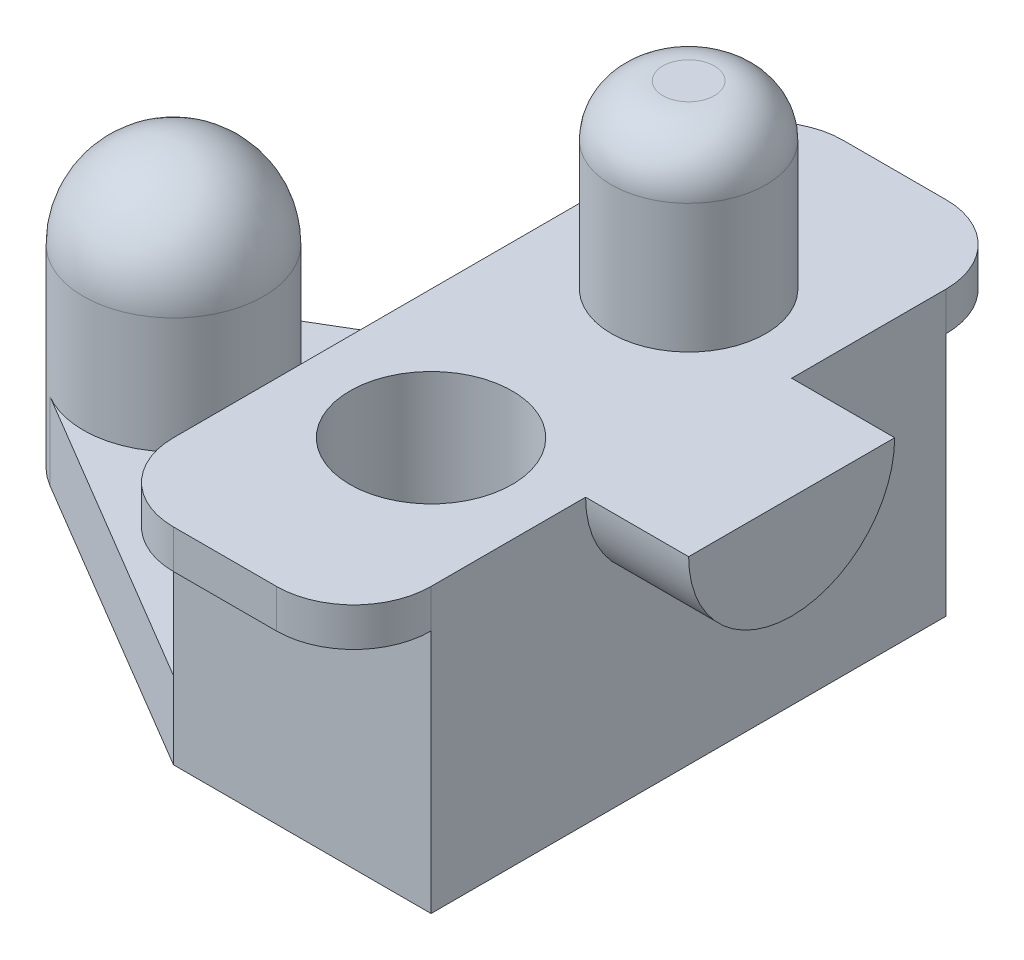
SolidWorks part; units mm, degrees
other "Markup1"
sketch "Sketch7" plane through (12, 7.5, 6.5) normal (0.0383, 0.9456, 0.3232) x (0.9932, -0.0006, -0.1161)
ref_plane "Front Plane" through (0, 0, 0) normal (0, 0, 1) x (1, 0, 0)
ref_plane "Top Plane" through (0, 0, 0) normal (0, 1, 0) x (1, 0, 0)
ref_plane "Right Plane" through (0, 0, 0) normal (1, 0, 0) x (0, 0, -1)
sketch "Sketch1" plane through (0, 0, 0) normal (0, 1, 0) x (1, 0, 0)
  line L0 (5, 5) -> (10, 5)
  line L1 (10, 5) -> (10, -5)
  line L2 (10, -5) -> (5, -5)
  line L3 (5, -5) -> (-0.8927, -1.5052)
  line L4 (5, 5) -> (-0.8927, 1.5052)
  arc A0 (-0.8927, 1.5052) -> (-0.8927, -1.5052) centre (0, 0) ccw
  point P11 (10, 0)
  dimension "D1" = 10
  dimension "D4" = 5
  dimension "D5" = 1.75
  dimension "D2" = 5
  dimension "D3" = 5
extrude "Boss-Extrude1" add sketch "Sketch1" against normal blind 1.5 contours L1 L2 L3 A0 L4 L0
sketch "Sketch2" plane through (0, 0, 0) normal (0, 1, 0) x (1, 0, 0)
  line L1 (5, 5) -> (10, 5)
  line L2 (5, 5) -> (5, -5)
  line L3 (5, -5) -> (10, -5)
  line L4 (10, 5) -> (10, -5)
  circle A0 centre (0, 0) radius 1.75
  dimension "D1" = 3.5
extrude "Boss-Extrude2" add sketch "Sketch2" along normal blind 4
sketch "Sketch3" plane through (0, 4, 0) normal (0, 1, 0) x (1, 0, 0)
  line L0 (5, 5) -> (10, 5)
  line L1 (6.5, 6.5) -> (8.5, 6.5)
  line L2 (10, -5) -> (10, 5) construction
  line L3 (5, 5) -> (5, -5) construction
  line L4 (-0.825, 0) -> (0.825, 0) construction
  line L5 (6.5, -6.5) -> (8.5, -6.5)
  line L6 (5, -5) -> (10, -5)
  arc A0 (8.5, 6.5) -> (10, 5) centre (8.5, 5) cw
  arc A1 (6.5, 6.5) -> (5, 5) centre (6.5, 5) ccw
  arc A2 (6.5, -6.5) -> (5, -5) centre (6.5, -5) cw
  arc A3 (8.5, -6.5) -> (10, -5) centre (8.5, -5) ccw
  dimension "D2" = 1.5
extrude "Boss-Extrude3" add sketch "Sketch3" against normal blind 0.75
fillet "Fillet1" radius 1.75 1 edges at (0, 4, 1.75)
sketch "Sketch4" plane through (0, 4, 0) normal (0, 1, 0) x (1, 0, 0)
  line L0 (5, 5) -> (5, -5) construction
  circle A0 centre (7.5, 2.5) radius 1.5
  dimension "D1" = 3
  dimension "D2" = 2.5
  dimension "D3" = 2.5
extrude "Boss-Extrude4" add sketch "Sketch4" along normal blind 3.5
fillet "Fillet2" radius 1 1 edges at (7.5, 7.5, -1)
sketch "Sketch5" plane through (0, 4, 0) normal (0, 1, 0) x (1, 0, 0)
  line L0 (5, 5) -> (5, -5) construction
  circle A0 centre (7.5, -2.5) radius 1.575
  dimension "D1" = 3.15
  dimension "D2" = 2.5
  dimension "D3" = 2.5
extrude "Cut-Extrude1" cut sketch "Sketch5" against normal blind 3.75
sketch "Sketch6" plane through (10, 0, 0) normal (1, 0, 0) x (0, 0, -1)
  line L0 (-5, 4) -> (5, 4) construction
  line L1 (-2, 4) -> (2, 4)
  arc A0 (-2, 4) -> (2, 4) centre (0, 4) ccw
  dimension "D1" = 4
extrude "Boss-Extrude5" add sketch "Sketch6" along normal blind 2
